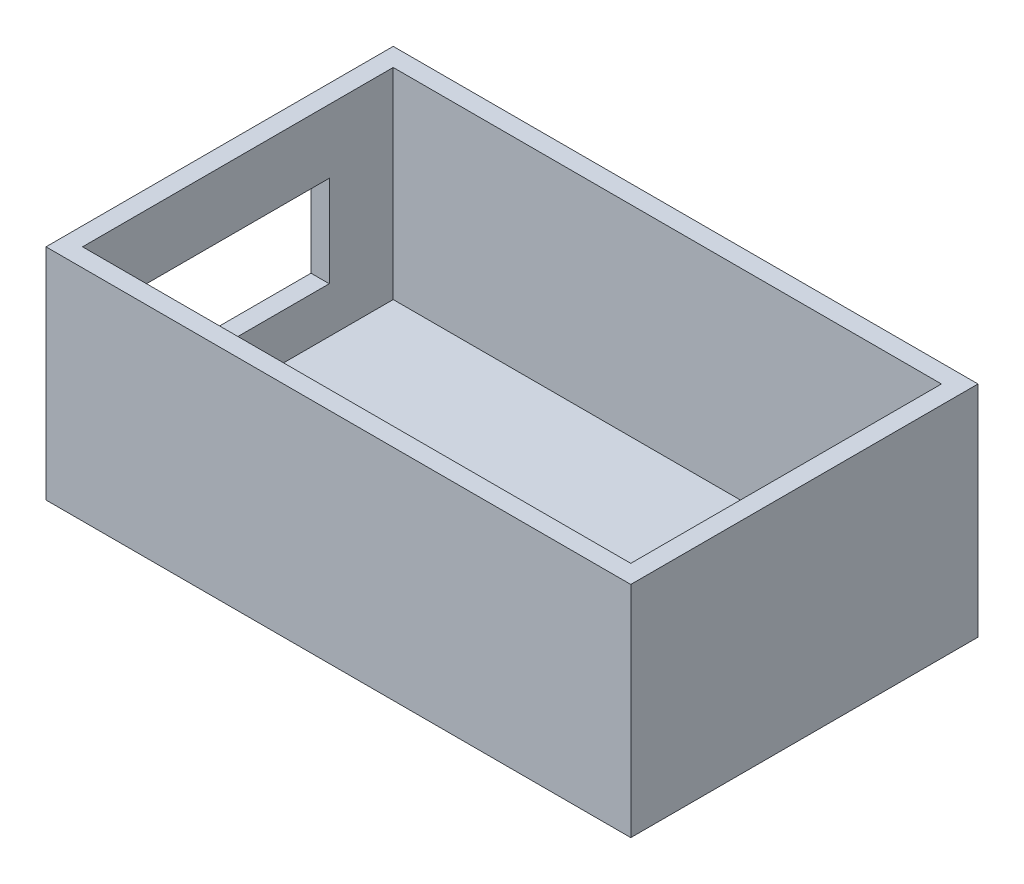
SolidWorks part; units mm, degrees
ref_plane "Alzado" through (0, 0, 0) normal (0, 0, 1) x (1, 0, 0)
ref_plane "Planta" through (0, 0, 0) normal (0, 1, 0) x (1, 0, 0)
ref_plane "Vista lateral" through (0, 0, 0) normal (1, 0, 0) x (0, 0, -1)
sketch "Croquis1" plane through (0, 0, 0) normal (0, 1, 0) x (1, 0, 0)
  line L0 (-1, -1) -> (-1, 18)
  line L1 (0, 0) -> (30, 0)
  line L2 (0, 0) -> (0, 17)
  line L3 (0, 17) -> (30, 17)
  line L4 (30, 0) -> (30, 17)
  line L5 (-1, 18) -> (31, 18)
  line L6 (31, -1) -> (31, 18)
  line L7 (-1, -1) -> (31, -1)
  dimension "D1" = 17
  dimension "D2" = 30
  dimension "D3" = 1
extrude "Saliente-Extruir1" add sketch "Croquis1" along normal blind 12 contours L2 L1 L4 L3 | L0 L5 L6 L7
extrude "Saliente-Extruir2" add sketch "Croquis1<3>" along normal blind 1 contours L1 L4 L3 L2 region at (15, 0, -8.5)
sketch "Croquis1<3>" plane through (0, 0, 0) normal (0, 1, 0) x (1, 0, 0) same geometry as "Croquis1"
sketch "Croquis2" plane through (-1, 0, 0) normal (-1, 0, 0) x (0, 0, 1)
  line L0 (-8.5, 12) -> (-8.5, 0)
  line L1 (1, 12) -> (-18, 12) construction
  line L2 (1, 0) -> (-18, 0) construction
  line L4 (-13.5, 8.5) -> (-3.5, 8.5)
  line L5 (-13.5, 8.5) -> (-13.5, 3.5)
  line L6 (-13.5, 3.5) -> (-3.5, 3.5)
  line L7 (-3.5, 8.5) -> (-3.5, 3.5)
  line L8 (-13.5, 8.5) -> (-3.5, 3.5) construction
  line L9 (-13.5, 3.5) -> (-3.5, 8.5) construction
  point P6 (-8.5, 6)
  dimension "D1" = 5
  dimension "D2" = 10
  dimension "D3" = 6
extrude "Cortar-Extruir1" cut sketch "Croquis2" against normal blind 1 contours L5 L6 L0 L4 | L7 L4 L0 L6 region at (-1, 6, -6) region at (-1, 6, -11)
